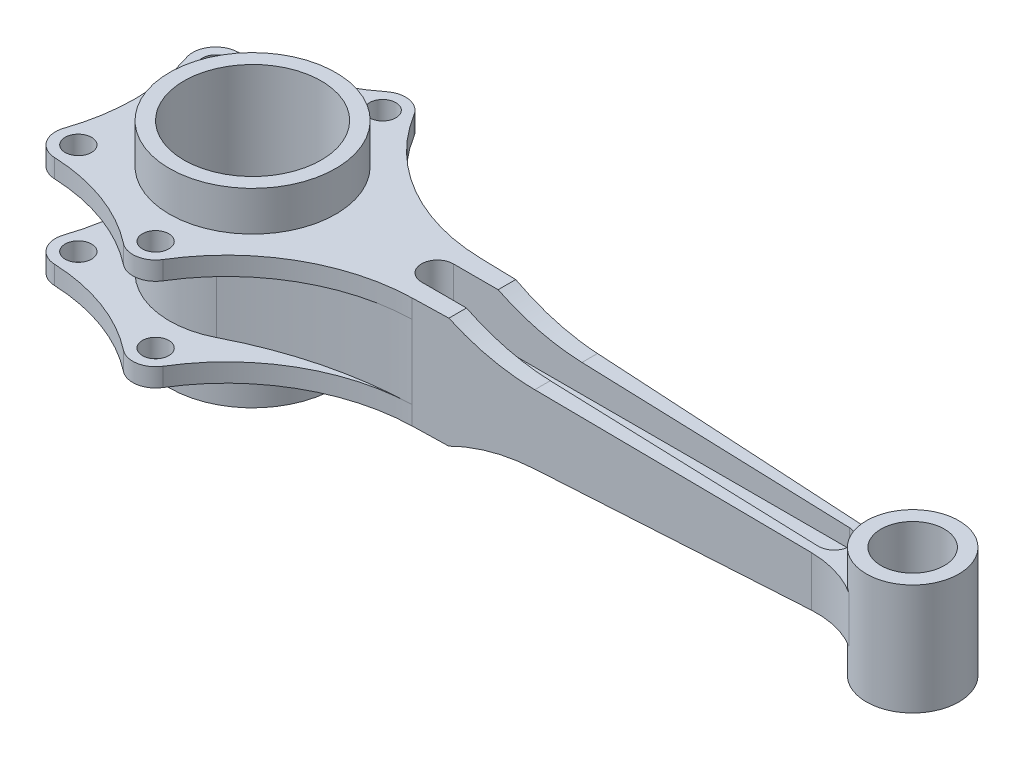
SolidWorks part; units mm, degrees
ref_plane "Front Plane" through (0, 0, 0) normal (0, 0, 1) x (1, 0, 0)
ref_plane "Top Plane" through (0, 0, 0) normal (0, 1, 0) x (1, 0, 0)
ref_plane "Right Plane" through (0, 0, 0) normal (1, 0, 0) x (0, 0, -1)
sketch "Sketch1" plane through (0, 0, 0) normal (0, 1, 0) x (1, 0, 0)
  line L0 (-34.65, 0) -> (34.65, 0) construction
  line L1 (0, 0) -> (250, 0) construction
  line L2 (234.9917, -9) -> (73.3643, -13)
  line L3 (234.9917, 9) -> (73.3643, 13)
  circle A0 centre (0, 0) radius 26
  circle A1 centre (0, 0) radius 31.5
  circle A2 centre (250, 0) radius 17.5
  circle A3 centre (250, 0) radius 12
  arc A4 (-40.3598, 34.6522) -> (-48.1974, 23.2086) centre (-40, 26) ccw
  arc A5 (13.6647, 47.5068) -> (0.9428, 49.827) centre (6.2702, 43) ccw
  arc A6 (13.6647, -47.5068) -> (0.9428, -49.827) centre (6.2702, -43) cw
  arc A7 (-40.3598, -34.6522) -> (-48.1974, -23.2086) centre (-40, -26) cw
  arc A8 (-48.1974, 23.2086) -> (-48.1974, -23.2086) centre (-116.3543, 0) cw
  arc A9 (-40.3598, 34.6522) -> (0.9428, 49.827) centre (-43.3513, 106.59) ccw
  arc A10 (-40.3598, -34.6522) -> (0.9428, -49.827) centre (-43.3513, -106.59) cw
  arc A11 (13.6647, -47.5068) -> (73.3643, -13) centre (75.1456, -84.978) cw
  arc A12 (13.6647, 47.5068) -> (73.3643, 13) centre (75.1456, 84.978) ccw
  point P30 (0, 0)
  point P35 (232.745, -2.9183)
  dimension "D2" = 35
  dimension "D3" = 24
  dimension "D4" = 72
  dimension "D5" = 72
  dimension "D6" = 72
  dimension "D11" = 72
  dimension "D1" = 250
  dimension "D7" = 26
  dimension "D8" = 18
  dimension "D9" = 26
  dimension "D10" = 17
extrude "Boss-Extrude4" add sketch "Sketch1" along normal mid plane 72 contours A0 A1 region at (-30.609, 0, 0)
extrude "Boss-Extrude5" add sketch "Sketch1<6>" along normal mid plane 42 contours A1 A2 L3 A12 A5 A9 A4 A8 A7 A10 A6 A11 L2 region at (68.171, 0, 0)
sketch "Sketch1<6>" plane through (0, 0, 0) normal (0, 1, 0) x (1, 0, 0) same geometry as "Sketch1"
extrude "Boss-Extrude6" add sketch "Sketch1<7>" along normal mid plane 42 separate body contours A2 A3 region at (232.995, 0, 0)
sketch "Sketch1<7>" plane through (0, 0, 0) normal (0, 1, 0) x (1, 0, 0) same geometry as "Sketch1"
sketch "Sketch3" plane through (0, 0, 0) normal (0, 1, 0) x (1, 0, 0)
  line L2 (73.3643, -13) -> (234.9917, -9)
  line L3 (234.9917, 9) -> (73.3643, 13)
  line L4 (73.3643, -13) -> (234.9917, -9)
  line L5 (234.9917, 9) -> (73.3643, 13)
  circle A0 centre (0, 0) radius 31.5 construction
  circle A1 centre (0, 0) radius 31.5
  arc A2 (14.3817, 28.0253) -> (73.3643, 13) centre (76.7436, 149.5481) ccw
  arc A3 (14.3817, -28.0253) -> (73.3643, -13) centre (76.7436, -149.5481) cw
  arc A10 (234.9917, 9) -> (234.9917, -9) centre (250, 0) ccw
  arc A11 (13.6647, 47.5068) -> (73.3643, 13) centre (75.1456, 84.978) ccw
  arc A12 (13.6647, 47.5068) -> (0.9428, 49.827) centre (6.2702, 43) ccw
  arc A13 (-40.3598, 34.6522) -> (0.9428, 49.827) centre (-43.3513, 106.59) ccw
  arc A14 (-40.3598, 34.6522) -> (-48.1974, 23.2086) centre (-40, 26) ccw
  arc A15 (-48.1974, -23.2086) -> (-48.1974, 23.2086) centre (-116.3543, 0) ccw
  arc A16 (-48.1974, -23.2086) -> (-40.3598, -34.6522) centre (-40, -26) ccw
  arc A17 (0.9428, -49.827) -> (-40.3598, -34.6522) centre (-43.3513, -106.59) ccw
  arc A18 (0.9428, -49.827) -> (13.6647, -47.5068) centre (6.2702, -43) ccw
  arc A19 (73.3643, -13) -> (13.6647, -47.5068) centre (75.1456, -84.978) ccw
  arc A20 (234.9917, 9) -> (234.9917, -9) centre (250, 0) ccw
  arc A21 (13.6647, 47.5068) -> (73.3643, 13) centre (75.1456, 84.978) ccw
  arc A22 (13.6647, 47.5068) -> (0.9428, 49.827) centre (6.2702, 43) ccw
  arc A23 (-40.3598, 34.6522) -> (0.9428, 49.827) centre (-43.3513, 106.59) ccw
  arc A24 (-40.3598, 34.6522) -> (-48.1974, 23.2086) centre (-40, 26) ccw
  arc A25 (-48.1974, -23.2086) -> (-48.1974, 23.2086) centre (-116.3543, 0) ccw
  arc A26 (-48.1974, -23.2086) -> (-40.3598, -34.6522) centre (-40, -26) ccw
  arc A27 (0.9428, -49.827) -> (-40.3598, -34.6522) centre (-43.3513, -106.59) ccw
  arc A28 (0.9428, -49.827) -> (13.6647, -47.5068) centre (6.2702, -43) ccw
  arc A29 (73.3643, -13) -> (13.6647, -47.5068) centre (75.1456, -84.978) ccw
  point P25 (0, 0)
  dimension "D1" = 0
extrude "Cut-Extrude2" cut sketch "Sketch3" against normal mid plane 28 contours A29 A3 A1 A2 A21 A22 A23 A24 A25 A26 A27 A28 region at (38.3148, 0, 21.2576)
hole_wizard "Ø10.0 (10) Diameter Hole1" positions "Sketch4" profile "Sketch6" hole size "Ø10.0" standard "ANSI Metric" end condition through all
sketch "Sketch4" plane through (0, 21, 0) normal (0, 1, 0) x (1, 0, 0)
  point P0 (6.2702, 43)
  point P3 (-40, 26)
  point P6 (-40, -26)
  point P9 (6.2702, -43)
sketch "Sketch6" plane through (6.2702, 21, -43) normal (1, 0, 0) x (0, 0, 1)
  line L0 (0, 0) -> (0, 57)
  line L1 (0, 57) -> (5, 57)
  line L2 (5, 57) -> (5, 0)
  line L5 (5, 0) -> (0, 0)
  line L11 (0, -6.35) -> (0, 107.95) construction
  dimension "Thru Hole Dia." = 10
  dimension "Thru Hole Depth" = 57
sketch "Sketch7" plane through (0, 0, 0) normal (0, 0, 1) x (1, 0, 0)
  line L0 (0, 0) -> (136.6762, 0) construction
  line L2 (234.9917, 21) -> (232.5, 21) construction
  line L3 (233.7458, 9) -> (118.7518, 13.0157)
  line L4 (234.9917, 21) -> (73.3643, 21) construction
  line L5 (87, 21) -> (233.7458, 21)
  line L6 (233.7458, 21) -> (250, 21)
  line L7 (262, 21) -> (238, 21) construction
  line L8 (250, 21) -> (250, 8.4324)
  line L9 (250, 8.4324) -> (233.7458, 9)
  arc A0 (118.7518, 13.0157) -> (87, 21) centre (121.474, 90.9682) cw
  dimension "D2" = 78
  dimension "D1" = 2
  dimension "D3" = 9
  dimension "D4" = 87
  dimension "D5" = 12.5676
  dimension "D6" = 16.2542
extrude "Cut-Extrude3" cut sketch "Sketch7" against normal through all both and the other way through all
mirror "Mirror1" about plane through (0, 0, 0) normal (0, 1, 0) of "Cut-Extrude3"
sketch "Sketch8" plane through (0, 0, 0) normal (0, 1, 0) x (1, 0, 0)
  line L0 (70, 0) -> (220, 0) construction
  line L1 (70, 6) -> (220, 6)
  line L2 (70, -6) -> (220, -6)
  arc A0 (70, 6) -> (70, -6) centre (70, 0) ccw
  arc A1 (220, -6) -> (220, 6) centre (220, 0) ccw
  circle A2 centre (250, 0) radius 12 construction
  point P3 (145, 0)
  point P8 (211.6302, 0)
  point P9 (0, 0)
  dimension "D2" = 6
  dimension "D3" = 30
  dimension "D1" = 150
extrude "Cut-Extrude5" cut sketch "Sketch8" along normal through all from offset 2.5
mirror "Mirror2" about plane through (0, 0, 0) normal (0, 1, 0) of "Cut-Extrude5"
combine bodies "Combine1" operation type add bodies to combine 114 107
fillet "Fillet1" radius 35 2 edges at (234.9917, 0, -9) (234.9917, 0, 9)
